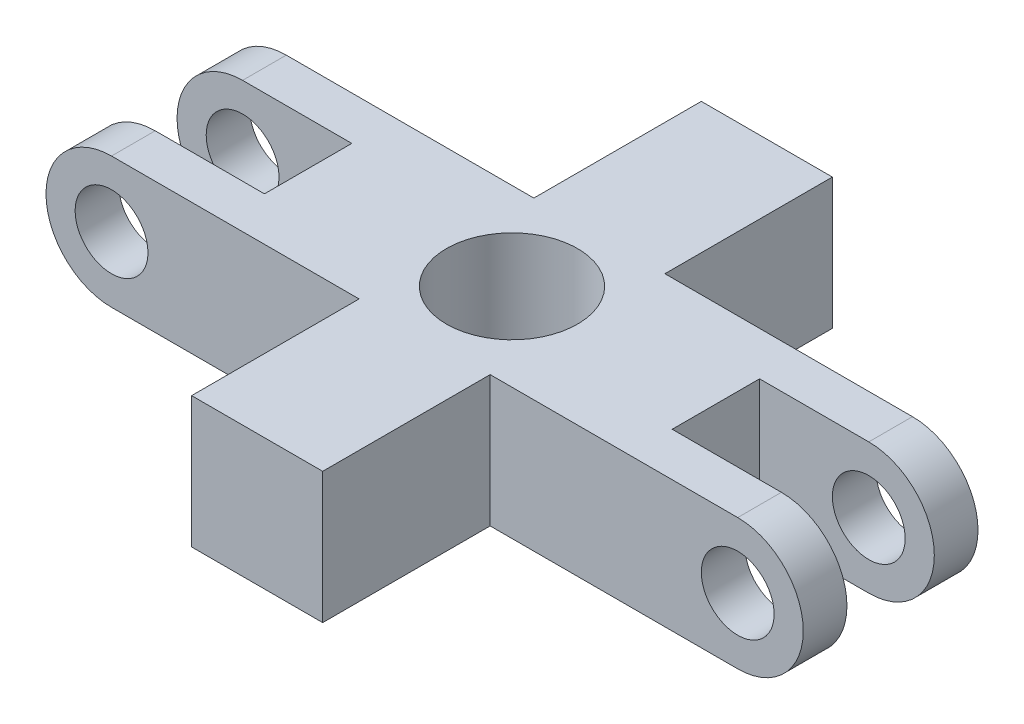
SolidWorks part; units mm, degrees
ref_plane "Front Plane" through (0, 0, 0) normal (0, 0, 1) x (1, 0, 0)
ref_plane "Top Plane" through (0, 0, 0) normal (0, 1, 0) x (1, 0, 0)
ref_plane "Right Plane" through (0, 0, 0) normal (1, 0, 0) x (0, 0, -1)
sketch "Sketch1" plane through (0, 0, 0) normal (0, 1, 0) x (1, 0, 0)
  line L0 (-26, 3) -> (-14, 3)
  line L1 (-26, 6) -> (-4.5, 6)
  line L2 (-26, 6) -> (-26, 3)
  line L3 (-26, -6) -> (-4.5, -6)
  line L4 (26, 6) -> (26, 3)
  line L5 (-26, 6) -> (26, -6) construction
  line L6 (-26, -6) -> (26, 6) construction
  line L7 (-14, 3) -> (-14, -3)
  line L8 (-14, -3) -> (-26, -3)
  line L9 (-26, -3) -> (-26, -6)
  line L10 (0, -55) -> (0, 55) construction
  line L11 (14, -3) -> (26, -3)
  line L12 (14, 3) -> (14, -3)
  line L13 (26, 3) -> (14, 3)
  line L14 (26, -3) -> (26, -6)
  line L15 (-4.5, -6) -> (-4.5, -17.5)
  line L16 (-4.5, 17.5) -> (4.5, 17.5)
  line L17 (-4.5, 17.5) -> (-4.5, 6)
  line L18 (-4.5, -17.5) -> (4.5, -17.5)
  line L19 (4.5, 17.5) -> (4.5, 6)
  line L20 (-4.5, 17.5) -> (4.5, -17.5) construction
  line L21 (-4.5, -17.5) -> (4.5, 17.5) construction
  line L22 (4.5, -6) -> (26, -6)
  line L23 (4.5, 6) -> (26, 6)
  line L24 (4.5, -6) -> (4.5, -17.5)
  circle A0 centre (0, 0) radius 4.5
  point P1 (0, 0)
  point P18 (-4.5, 0)
  point P19 (0, 4.5)
  dimension "D1" = 9
  dimension "D2" = 26
  dimension "D3" = 6
  dimension "D4" = 12
  dimension "D5" = 12
  dimension "D6" = 3
  dimension "D7" = 9
  dimension "D8" = 35
extrude "Boss-Extrude1" add sketch "Sketch1" along normal mid plane 9
sketch "Sketch2" plane through (0, 0, -3) normal (0, 0, 1) x (1, 0, 0)
  circle A0 centre (-21.5, 0) radius 2.5
  point P4 (-24, 0)
  dimension "D1" = 5
  dimension "D2" = 21.5
fillet "Fillet2" 2 edges at (-26, 4.5, 4.5) (-26, -4.5, 4.5) type full round first side face at (0, 4.5, 0) second side face at (0, -4.5, 0) middle face at (-26, 0, 4.5)
fillet "Fillet3" 2 edges at (-26, 4.5, -4.5) (-26, -4.5, -4.5) type full round first side face at (0.45, 4.5, 0) second side face at (0.45, -4.5, 0) middle face at (-26, 0, -4.5)
fillet "Fillet4" 2 edges at (26, 4.5, -4.5) (26, -4.5, -4.5) type full round first side face at (0.9, 4.5, 0) second side face at (0.9, -4.5, 0) middle face at (26, 0, -4.5)
fillet "Fillet5" 2 edges at (26, 4.5, 4.5) (26, -4.5, 4.5) type full round first side face at (0.45, 4.5, 0) second side face at (0.45, -4.5, 0) middle face at (26, 0, 4.5)
extrude "Cut-Extrude1" cut sketch "Sketch2" along normal through all and the other way through all contours A0
mirror "Mirror1" about plane through (0, 0, 0) normal (1, 0, 0) of "Cut-Extrude1"
